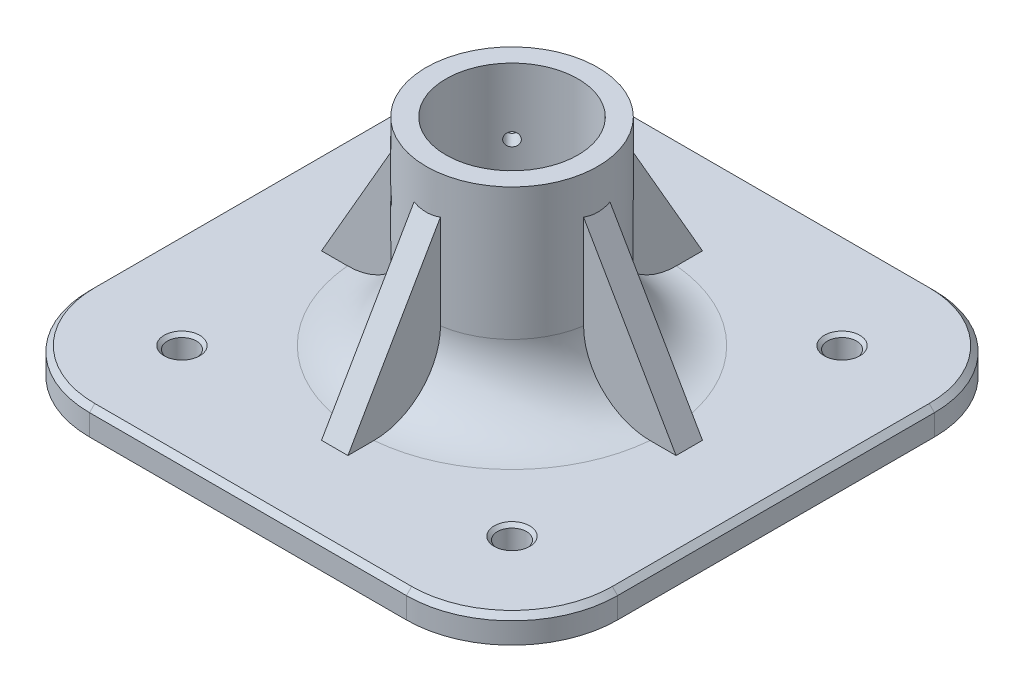
SolidWorks part; units mm, degrees
material "Cast Carbon Steel"
ref_plane "Front Plane" through (0, 0, 0) normal (0, 0, 1) x (1, 0, 0)
ref_plane "Top Plane" through (0, 0, 0) normal (0, 1, 0) x (1, 0, 0)
ref_plane "Right Plane" through (0, 0, 0) normal (1, 0, 0) x (0, 0, -1)
sketch "Sketch2" plane through (0, 0, 0) normal (0, 1, 0) x (1, 0, 0)
  line L1 (-100, -100) -> (100, -100)
  line L2 (-100, -100) -> (-100, 100)
  line L3 (-100, 100) -> (100, 100)
  line L4 (100, -100) -> (100, 100)
  line L5 (0, 100) -> (0, -100) construction
  line L6 (-100, 0) -> (100, 0) construction
  point P0 (0, 0)
  dimension "D1" = 200
  dimension "D2" = 200
extrude "Boss-Extrude1" add sketch "Sketch2" along normal blind 10
sketch "Sketch3" plane through (0, 10, 0) normal (0, 1, 0) x (1, 0, 0)
  circle A0 centre (0, 0) radius 32.5
  circle A1 centre (0, 0) radius 25
  dimension "D1" = 65
  dimension "D2" = 50
extrude "Boss-Extrude2" add sketch "Sketch3" along normal blind 75
sketch "Sketch4" plane through (0, 10, 0) normal (0, 1, 0) x (1, 0, 0)
  line L1 (-62.5, -62.5) -> (62.5, -62.5) construction
  line L2 (-62.5, -62.5) -> (-62.5, 62.5) construction
  line L3 (-62.5, 62.5) -> (62.5, 62.5) construction
  line L4 (62.5, -62.5) -> (62.5, 62.5) construction
  line L5 (0, 62.5) -> (0, -62.5) construction
  line L6 (-62.5, 0) -> (62.5, 0) construction
  point P1 (62.5, 62.5)
  point P2 (-62.5, -62.5)
  point P3 (-62.5, 62.5)
  point P8 (62.5, -62.5)
  point P55 (-62.5, 62.5)
  point P57 (62.5, 62.5)
  point P59 (62.5, -62.5)
  point P61 (-62.5, -62.5)
  dimension "D1" = 125
  dimension "D2" = 125
hole_wizard "M10 Clearance Hole1" positions "Sketch4" profile "Sketch5" hole size "M10" standard "ANSI Metric" end condition through all
sketch "Sketch5" plane through (-62.5, 10, 62.5) normal (1, 0, 0) x (0, 0, 1)
  line L0 (0, 0) -> (0, 10)
  line L1 (0, 10) -> (5.5, 10)
  line L2 (5.5, 10) -> (5.5, 1.25)
  line L3 (5.5, 1.25) -> (6.75, 0)
  line L5 (6.75, 0) -> (0, 0)
  line L6 (-5.5, 1.25) -> (-6.75, 0) construction
  line L11 (0, -6.35) -> (0, 107.95) construction
  dimension "Thru Hole Dia." = 11
  dimension "Thru Hole Depth" = 10
  dimension "Near C'Sink Dia." = 13.5
  dimension "Near C'Sink Angle" = 90
ref_plane "Set Screw Plane" through (-22.981, 0, 22.981) normal (-0.7071, 0, 0.7071) x (0, -1, 0)
sketch "Sketch6" plane through (-22.981, 0, 22.981) normal (-0.7071, 0, 0.7071) x (0, -1, 0)
  line L0 (0, 0) -> (-60, 0) construction
  dimension "D1" = 60
hole_wizard "M6x1.0 Tapped Hole1" positions "Sketch10" profile "Sketch8" tap size "M6x1.0" standard "ANSI Metric" end condition up to next
sketch "Sketch10" plane through (-22.981, 0, 22.981) normal (-0.7071, 0, 0.7071) x (0, -1, 0)
  point P0 (-60, 0)
sketch "Sketch8" plane through (-22.981, 60, 22.981) normal (0, 1, 0) x (0.7071, 0, 0.7071)
  line L0 (0, 0) -> (0, 7.5)
  line L1 (0, 7.5) -> (2.5, 7.5)
  line L2 (2.5, 7.5) -> (2.5, 1.25)
  line L3 (2.5, 1.25) -> (3.75, 0)
  line L5 (3.75, 0) -> (0, 0)
  line L6 (-2.5, 1.25) -> (-3.75, 0) construction
  line L11 (0, -6.35) -> (0, 107.95) construction
  dimension "Thru Tap Drill Dia." = 5
  dimension "Thru Tap Drill Depth" = 7.5
  dimension "Near C'Sink Dia." = 7.5
  dimension "Near C'Sink Angle" = 90
cosmetic thread "Hole Thread1" parameters "D2"=6
pattern_circular "CirPattern1" count 2 over 90 about axis through (0, 85, 0) along (0, -1, 0) of "M6x1.0 Tapped Hole1"
cosmetic thread "Hole Thread2" parameters "D2"=6
sketch "Sketch13" plane through (0, 0, 0) normal (0, 0, 1) x (1, 0, 0)
  line L0 (-32.5, 70) -> (-67.141, 10)
  line L1 (-32.5, 85) -> (-32.5, 10) construction
  line L2 (-100, 10) -> (100, 10) construction
  dimension "D1" = 60
  dimension "D2" = 60
rib "Rib5" sketch "Sketch13" sketch "Sketch13" thickness 10 extrusion direction parallel to sketch draft on no parameters "D1"=10
pattern_circular "CirPattern2" count 4 every 90 about axis through (0, 85, 0) along (0, -1, 0) of "Rib5"
fillet "Fillet1" radius 25 4 edges at (-22.981, 10, -22.981) (22.981, 10, -22.981) (22.981, 10, 22.981) (-22.981, 10, 22.981)
fillet "Fillet2" radius 40 4 edges at (-100, 5, 100) (-100, 5, -100) (100, 5, -100) (100, 5, 100)
chamfer "Chamfer1" distance 2 angle 45 8 edges at (0, 10, -100) (-88.2843, 10, -88.2843) (88.2843, 10, -88.2843) (-100, 10, 0) (100, 10, 0) (-88.2843, 10, 88.2843) (88.2843, 10, 88.2843) (0, 10, 100)
